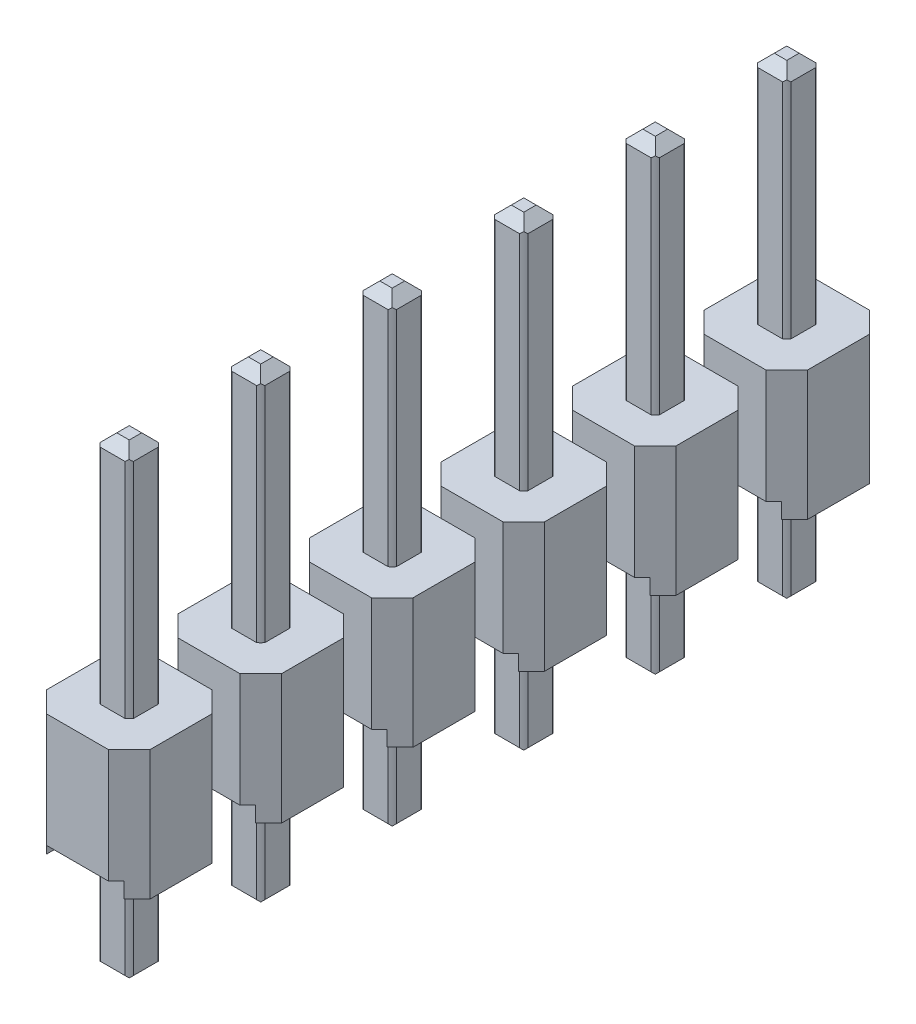
SolidWorks part; units mm, degrees
ref_plane "Front Plane" through (0, 0, 0) normal (0, 0, 1) x (1, 0, 0)
ref_plane "Top Plane" through (0, 0, 0) normal (0, 1, 0) x (1, 0, 0)
ref_plane "Right Plane" through (0, 0, 0) normal (1, 0, 0) x (0, 0, -1)
sketch "Sketch3" plane through (0, 0, 0) normal (0, 1, 0) x (1, 0, 0)
  line L1 (-1, -1) -> (1, -1)
  line L2 (-1, -1) -> (-1, 1)
  line L3 (-1, 1) -> (1, 1)
  line L4 (1, -1) -> (1, 1)
  line L5 (-1, -1) -> (1, 1) construction
  line L6 (-1, 1) -> (1, -1) construction
  point P0 (0, 0)
  dimension "D1" = 2
extrude "Boss-Extrude3" add sketch "Sketch3" along normal blind 2.5
sketch "Sketch4" plane through (0, 0, 1) normal (0, 0, 1) x (1, 0, 0)
  line L0 (-1, 0) -> (1, 0) construction
  line L1 (-0.75, 0) -> (0.75, 0)
  line L2 (-0.75, 0) -> (-0.75, 0.3)
  line L3 (-0.75, 0.3) -> (0.75, 0.3)
  line L4 (0.75, 0) -> (0.75, 0.3)
  line L5 (1, 2.5) -> (1, 0) construction
  line L6 (-1, 2.5) -> (-1, 0) construction
  dimension "D1" = 0.25
  dimension "D2" = 0.25
  dimension "D3" = 0.3
extrude "Cut-Extrude1" cut sketch "Sketch4" against normal through all
chamfer "Chamfer1" distance 0.4 angle 45 4 edges at (-1, 1.25, 1) (-1, 1.25, -1) (1, 1.25, -1) (1, 1.25, 1)
sketch "Sketch5" plane through (0, 0, 0) normal (0, 1, 0) x (1, 0, 0)
  line L1 (-0.24, -0.32) -> (0.24, -0.32)
  line L2 (-0.32, -0.24) -> (-0.32, 0.24)
  line L3 (-0.24, 0.32) -> (0.24, 0.32)
  line L4 (0.32, -0.24) -> (0.32, 0.24)
  line L5 (-0.2828, -0.2828) -> (0.2828, 0.2828) construction
  line L6 (-0.2828, 0.2828) -> (0.2828, -0.2828) construction
  arc A0 (0.32, 0.24) -> (0.24, 0.32) centre (0, 0) ccw
  arc A1 (-0.24, 0.32) -> (-0.32, 0.24) centre (0, 0) ccw
  arc A2 (-0.32, -0.24) -> (-0.24, -0.32) centre (0, 0) ccw
  arc A3 (0.24, -0.32) -> (0.32, -0.24) centre (0, 0) ccw
  dimension "D1" = 0.8
extrude "Boss-Extrude4" add sketch "Sketch5" along normal blind 7 and the other way blind 2
chamfer "Chamfer2" distance 0.2 angle 45 8 edges at (0.32, -2, 0) (0, -2, -0.32) (-0.32, -2, 0) (0, -2, 0.32) (0, 7, 0.32) (-0.32, 7, 0) (0, 7, -0.32) (0.32, 7, 0)
pattern_linear "LPattern1" count 6 spacing 2.54 along (0, 0, -1) of bodies 105
